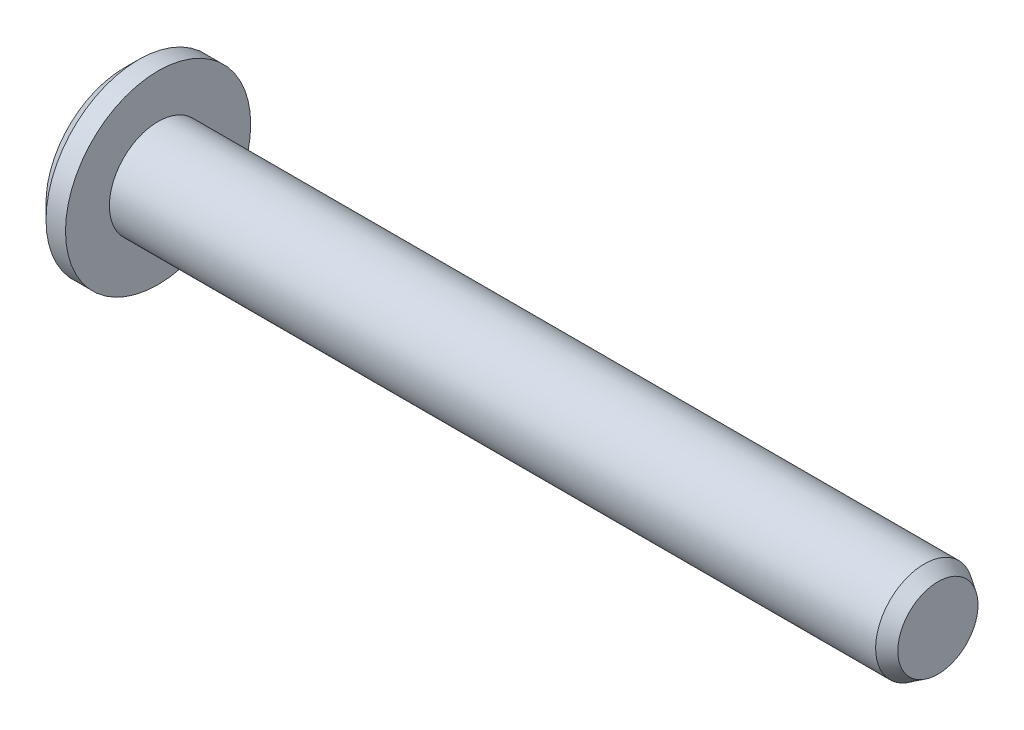
SolidWorks part; units mm, degrees
ref_plane "Front Plane" through (0, 0, 0) normal (0, 0, 1) x (1, 0, 0)
ref_plane "Top Plane" through (0, 0, 0) normal (0, 1, 0) x (1, 0, 0)
ref_plane "Right Plane" through (0, 0, 0) normal (1, 0, 0) x (0, 0, -1)
ref_plane "Plane1" through (5, 0, 0) normal (1, 0, 0) x (0, 0, -1)
sketch "Sketch1" plane through (0, 0, 0) normal (0, 0, 1) x (1, 0, 0)
  line L0 (41.75, 0) -> (41.75, 2.0572)
  line L1 (41.055, 2.5) -> (1.75, 2.5)
  line L2 (1.75, 2.5) -> (1.75, 4.75)
  line L3 (1.75, 4.75) -> (0, 4.75)
  line L4 (0, 0) -> (101.6, 0) construction
  line L7 (41.75, 0) -> (0, 0)
  line L9 (0, 4.75) -> (0, 0)
  line L10 (41.75, 2.0572) -> (41.055, 2.5)
  line L14 (0, 4.75) -> (0, 0) construction
  dimension "D1" = 40
  dimension "D2" = 2.5
  dimension "D3" = 1.75
  dimension "D4" = 122.5
  dimension "D5" = 2.0572
  dimension "D6" = 2.25
revolve "Revolve1" add sketch "Sketch1" angle 360 about L4
sketch "Sketch2" plane through (1.75, 0, 0) normal (1, 0, 0) x (0, 0, -1)
  circle A0 centre (0, 0) radius 2.55
  dimension "D1" = 5.1
curve "Helix/Spiral1" pitch 0.8 height 64 turns 80
sketch "Sketch4" plane through (0, 0, 0) normal (0, 0, 1) x (1, 0, 0)
  line L0 (26.9044, 2.5) -> (26.1244, 2.5)
  line L1 (26.9044, 2.5) -> (26.5079, 2.1165)
  line L2 (26.5079, 2.1165) -> (26.1244, 2.5)
  dimension "D1" = 0.78
  dimension "D2" = 45
  dimension "D3" = 2.5
sweep "Cut-Sweep2" [suppressed] cut profiles "Sketch4" path "Helix/Spiral1"
sketch "Sketch5" plane through (0, 0, 0) normal (-1, 0, 0) x (0, 0, 1)
  line L1 (1.5, -0.866) -> (1.5, 0.866)
  line L2 (1.5, 0.866) -> (0, 1.7321)
  line L3 (0, 1.7321) -> (-1.5, 0.866)
  line L4 (-1.5, 0.866) -> (-1.5, -0.866)
  line L5 (-1.5, -0.866) -> (0, -1.7321)
  line L6 (0, -1.7321) -> (1.5, -0.866)
  circle A0 centre (0, 0) radius 1.5 construction
  dimension "D1" = 3
extrude "Cut-Extrude1" cut sketch "Sketch5" against normal blind 1
chamfer "Chamfer1" distance 0.75 angle 45 1 edges at (0, -4.75, 0)
